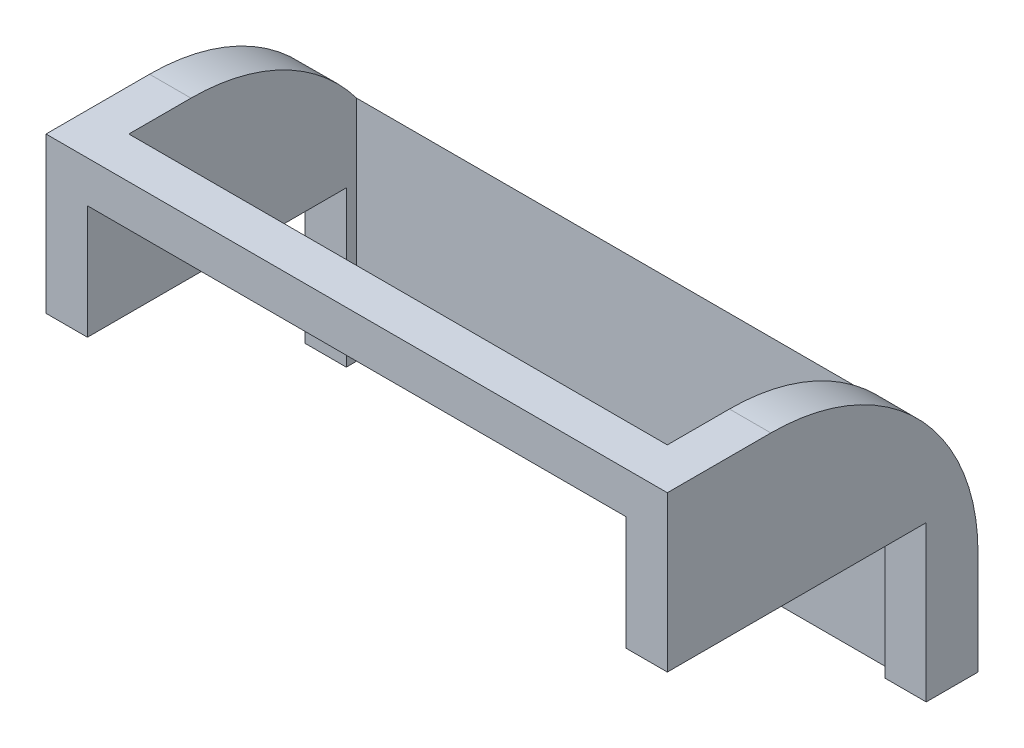
SolidWorks part; units mm, degrees
material "Alumina"
ref_plane "Front Plane" through (0, 0, 0) normal (0, 0, 1) x (1, 0, 0)
ref_plane "Top Plane" through (0, 0, 0) normal (0, 1, 0) x (1, 0, 0)
ref_plane "Right Plane" through (0, 0, 0) normal (1, 0, 0) x (0, 0, -1)
sketch "Sketch12" plane through (0, 0, 0) normal (0, 1, 0) x (1, 0, 0)
  line L1 (-15, -7.5) -> (15, -7.5)
  line L2 (-15, -7.5) -> (-15, 7.5)
  line L3 (-15, 7.5) -> (15, 7.5)
  line L4 (15, -7.5) -> (15, 7.5)
  line L5 (-15, -7.5) -> (15, 7.5) construction
  line L6 (-15, 7.5) -> (15, -7.5) construction
  point P0 (0, 0)
  dimension "D1" = 15
  dimension "D2" = 30
extrude "Boss-Extrude4" add sketch "Sketch12" along normal blind 15
fillet "Fillet1" radius 10 1 edges at (0, 15, -7.5)
sketch "Sketch13" plane through (0, 0, 0) normal (0, -1, 0) x (1, 0, 0)
  line L1 (13, -5.5) -> (-13, -5.5)
  line L2 (13, -5.5) -> (13, 5.5)
  line L3 (13, 5.5) -> (-13, 5.5)
  line L4 (-13, -5.5) -> (-13, 5.5)
  line L8 (-15, -7.5) -> (-15, 7.5) construction
  line L9 (15, -7.5) -> (-15, -7.5) construction
  line L11 (15, 7.5) -> (15, -7.5) construction
  dimension "D1" = 2
  dimension "D2" = 2
  dimension "D3" = 11
  dimension "D4" = 2
extrude "Cut-Extrude8" cut sketch "Sketch13" against normal through all both and the other way through all
sketch "Sketch14" plane through (0, 0, 7.5) normal (0, 0, 1) x (1, 0, 0)
  line L0 (-15, 15) -> (15, 15) construction
  line L1 (-13, 2) -> (13, 2)
  line L2 (-13, 2) -> (-13, 13)
  line L3 (-13, 13) -> (13, 13)
  line L4 (13, 2) -> (13, 13)
  line L5 (-15, 15) -> (-15, 0) construction
  line L6 (15, 15) -> (15, 0) construction
  line L7 (-15, 0) -> (15, 0) construction
  dimension "D1" = 2
  dimension "D2" = 2
  dimension "D3" = 2
  dimension "D4" = 2
extrude "Cut-Extrude9" cut sketch "Sketch14" against normal blind 10
sketch "Sketch15" plane through (15, 0, 0) normal (1, 0, 0) x (0, 0, -1)
  line L1 (-7.5, 0) -> (5, 0)
  line L2 (-7.5, 0) -> (-7.5, 7.5)
  line L3 (-7.5, 7.5) -> (5, 7.5)
  line L4 (5, 0) -> (5, 7.5)
  dimension "D1" = 7.5
  dimension "D2" = 12.5
extrude "Cut-Extrude10" cut sketch "Sketch15" against normal through all both and the other way through all
scale "Scale1" scale about centroid uniform scaling yes scale factor 6
